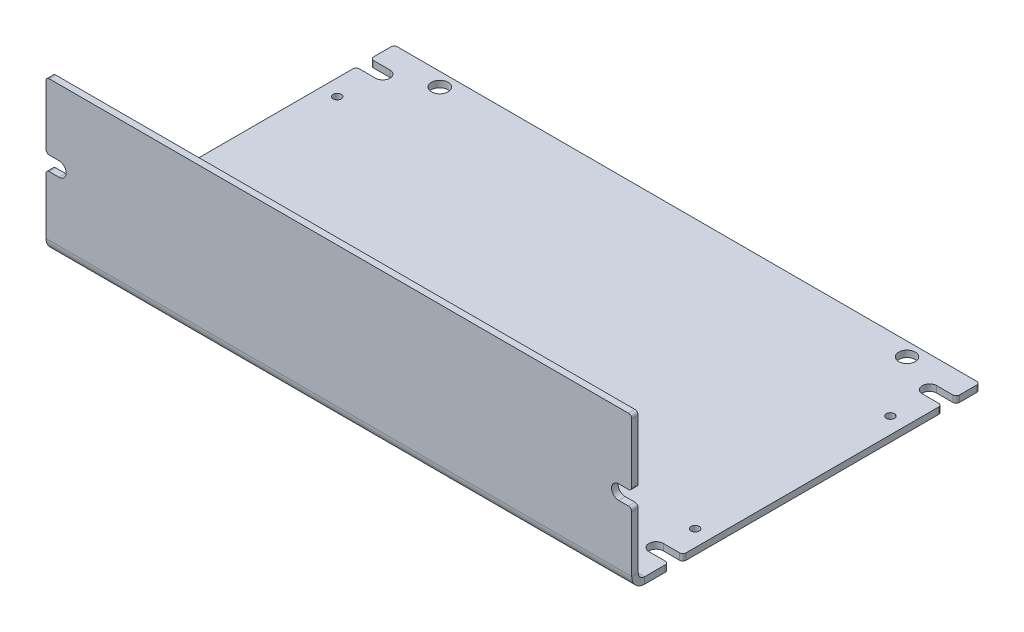
SolidWorks part; units mm, degrees
note: The reader was unsure of these and kept them because the rebuilt part matched: flange length of "Edge-Flange1".
material "AISI 304"
ref_plane "Front Plane" through (0, 0, 0) normal (0, 0, 1) x (1, 0, 0)
ref_plane "Top Plane" through (0, 0, 0) normal (0, 1, 0) x (1, 0, 0)
ref_plane "Right Plane" through (0, 0, 0) normal (1, 0, 0) x (0, 0, -1)
sketch "Sketch1" plane through (0, 0, 0) normal (0, 1, 0) x (1, 0, 0)
  line L1 (-90, 51.5) -> (90, 51.5)
  line L2 (-90, 51.5) -> (-90, -51.5)
  line L3 (-90, -51.5) -> (90, -51.5)
  line L4 (90, 51.5) -> (90, -51.5)
  line L5 (-90, 51.5) -> (90, -51.5) construction
  line L6 (-90, -51.5) -> (90, 51.5) construction
  point P0 (0, 0)
  dimension "D1" = 180
  dimension "D2" = 103
base flange "Base-Flange1" sketch "Sketch1" thickness 2 reverse thickness direction no parameters "D1"=2
edge flange "Edge-Flange1" sketch "Sketch8" flange angle 90 flange length 47 flange position bend outside bend radius 2 thickness 2 relief rectangular parameters "D6"=10
sketch "Sketch8" plane through (0, 0, -51.5) normal (0, 0, -1) x (-1, 0, 0)
  line L0 (-90, 24.7) -> (-86, 24.7)
  line L2 (-90, 0) -> (-90, 20.3)
  line L3 (-90, 45) -> (90, 45)
  line L4 (90, 45) -> (90, 24.7)
  line L5 (-86, 20.3) -> (-90, 20.3)
  line L7 (-90, 0) -> (90, 0) construction
  line L8 (-90, 0) -> (90, 0)
  line L9 (0, 0) -> (0, 45) construction
  line L10 (86, 20.3) -> (90, 20.3)
  line L11 (90, 24.7) -> (86, 24.7)
  line L12 (0, 22.5) -> (-86, 22.5) construction
  line L13 (-90, 24.7) -> (-90, 45)
  line L14 (90, 20.3) -> (90, 0)
  arc A0 (-86, 24.7) -> (-86, 20.3) centre (-86, 22.5) cw
  arc A1 (86, 24.7) -> (86, 20.3) centre (86, 22.5) ccw
  dimension "D2" = 2.2
  dimension "D1" = 45
  dimension "D3" = 4
bend "EdgeBend1" bend radius 2 bend angle 90 parameters "D5"=1
hole_wizard "Ø5.1 (5.1) Diameter Hole1" positions "Sketch9" profile "Sketch10" hole size "Ø5.1" standard "ISO" end condition through all
sketch "Sketch9" plane through (0, -2, 0) normal (0, -1, 0) x (-1, 0, 0)
  line L0 (90, -51.5) -> (-90, -51.5) construction
  point P0 (-71.8, -47.3)
  dimension "D1" = 4.2
  dimension "D2" = 71.8
sketch "Sketch10" plane through (71.8, -2, 47.3) normal (1, 0, 0) x (0, 0, -1)
  line L0 (0, 0) -> (0, 47)
  line L1 (0, 47) -> (2.55, 47)
  line L2 (2.55, 47) -> (2.55, 0)
  line L5 (2.55, 0) -> (0, 0)
  line L11 (0, -6.35) -> (0, 107.95) construction
  dimension "Thru Hole Dia." = 5.1
  dimension "Thru Hole Depth" = 47
pattern_linear "LPattern1" count 2 spacing 143.6 along (-1, 0, 0) count 2 spacing 93.6 along (0, 0, -1) of "Ø5.1 (5.1) Diameter Hole1"
hole_wizard "M3 Tapped Hole1" positions "Sketch11" profile "Sketch12" tap size "M3" standard "ISO" end condition through all
sketch "Sketch11" plane through (0, 0, 0) normal (0, 1, 0) x (1, 0, 0)
  line L0 (-90, 51.5) -> (-90, -51.5) construction
  line L1 (-90, -51.5) -> (90, -51.5) construction
  line L2 (0, 1) -> (0, -51.5) construction
  line L6 (0, 1) -> (90, 1) construction
  line L7 (90, -51.5) -> (90, 51.5) construction
  circle A0 centre (-71.8, -47.3) radius 2.55 construction
  point P0 (-85, -29)
  point P22 (85, -29)
  point P45 (-85, 31)
  point P46 (85, 31)
  dimension "D2" = 18.3
  dimension "D1" = 5
  dimension "D3" = 30
sketch "Sketch12" plane through (-85, 0, 29) normal (1, 0, 0) x (0, 0, 1)
  line L0 (0, 0) -> (0, 2)
  line L1 (0, 2) -> (1.25, 2)
  line L2 (1.25, 2) -> (1.25, 0)
  line L5 (1.25, 0) -> (0, 0)
  line L11 (0, -6.35) -> (0, 107.95) construction
  dimension "Thru Tap Drill Dia." = 2.5
  dimension "Thru Tap Drill Depth" = 2
cosmetic thread "Hole Thread1"
cosmetic thread "Hole Thread5"
cosmetic thread "Hole Thread6"
cosmetic thread "Hole Thread7"
sketch "Sketch13" plane through (0, 0, 0) normal (0, 1, 0) x (1, 0, 0)
  line L0 (-90, 44.2) -> (-84, 44.2)
  line L1 (-90, 51.5) -> (-90, -51.5) construction
  line L2 (-84, 39.8) -> (-90, 39.8)
  line L3 (-90, 39.8) -> (-90, 44.2)
  line L4 (0, 0) -> (-87.5, 0) construction
  line L5 (0, 0) -> (0, 55.5) construction
  line L6 (-90, 55.5) -> (90, 55.5) construction
  line L7 (-90, -39.8) -> (-90, -44.2)
  line L8 (-84, -39.8) -> (-90, -39.8)
  line L9 (-90, -44.2) -> (-84, -44.2)
  line L10 (90, -44.2) -> (84, -44.2)
  line L11 (84, -39.8) -> (90, -39.8)
  line L12 (90, -39.8) -> (90, -44.2)
  line L13 (90, 39.8) -> (90, 44.2)
  line L14 (84, 39.8) -> (90, 39.8)
  line L15 (90, 44.2) -> (84, 44.2)
  arc A0 (-84, 44.2) -> (-84, 39.8) centre (-84, 42) cw
  arc A1 (-84, -44.2) -> (-84, -39.8) centre (-84, -42) ccw
  arc A2 (84, -44.2) -> (84, -39.8) centre (84, -42) cw
  arc A3 (84, 44.2) -> (84, 39.8) centre (84, 42) ccw
  dimension "D1" = 2.2
  dimension "D2" = 6
  dimension "D3" = 42
extrude "Cut-Extrude1" cut sketch "Sketch13" against normal through all normal cut yes
fillet "Fillet1" radius 1 16 edges at (-90, 45, -54.5) (-90, -1, 51.5) (90, -1, 51.5) (90, -1, 44.2) (90, -1, 39.8) (90, -1, -39.8) (90, -1, -44.2) (-90, -1, -44.2) (-90, -1, -39.8) (-90, -1, 44.2) (-90, -1, 39.8) (90, 45, -54.5) (90, 24.7, -54.5) (90, 20.3, -54.5) (-90, 24.7, -54.5) (-90, 20.3, -54.5)
move or copy body "Body-Move/Copy1" bodies to move or copy 123 copy no rotation origin (0, 0, 0) rotation axis (0, 1, 0) rotation angle 180
sketch "Bend-Lines1" [suppressed] plane through (0, 0, 0) normal (0, 1, 0) x (1, 0, 0)
sketch "Bounding-Box1" [suppressed] plane through (0, 0, 0) normal (0, 1, 0) x (1, 0, 0)
sheet metal parameters "Sheet-Metal17" thickness 2 parameters "D1"=3
flat pattern "Flat-Pattern17" [suppressed]
sketch "Bend-Lines2" plane through (0, 0, 0) normal (0, 1, 0) x (1, 0, 0)
sketch "Bounding-Box2" [suppressed] plane through (0, 0, 0) normal (0, 1, 0) x (1, 0, 0)
sheet metal parameters "Sheet-Metal18" thickness 2 parameters "D1"=3
flat pattern "Flat-Pattern17" [suppressed]
sketch "Bend-Lines2" plane through (0, 0, 0) normal (0, 1, 0) x (1, 0, 0)
sketch "Bounding-Box2" [suppressed] plane through (0, 0, 0) normal (0, 1, 0) x (1, 0, 0)
bend of the flat pattern "Flatten-<EdgeBend1>1"
sheet metal parameters "Sheet-Metal19" thickness 2 parameters "D1"=3
flat pattern "Flat-Pattern17" [suppressed]
sketch "Bend-Lines2" plane through (0, 0, 0) normal (0, 1, 0) x (1, 0, 0)
sketch "Bounding-Box2" [suppressed] plane through (0, 0, 0) normal (0, 1, 0) x (1, 0, 0)
bend of the flat pattern "Flatten-<EdgeBend1>1"
sheet metal parameters "Sheet-Metal20" thickness 2 parameters "D1"=3
flat pattern "Flat-Pattern17" [suppressed]
sketch "Bend-Lines2" plane through (0, 0, 0) normal (0, 1, 0) x (1, 0, 0)
sketch "Bounding-Box2" [suppressed] plane through (0, 0, 0) normal (0, 1, 0) x (1, 0, 0)
bend of the flat pattern "Flatten-<EdgeBend1>1"
sheet metal parameters "Sheet-Metal21" thickness 2 parameters "D1"=3
flat pattern "Flat-Pattern17" [suppressed]
sketch "Bend-Lines2" plane through (0, 0, 0) normal (0, 1, 0) x (1, 0, 0)
sketch "Bounding-Box2" [suppressed] plane through (0, 0, 0) normal (0, 1, 0) x (1, 0, 0)
bend of the flat pattern "Flatten-<EdgeBend1>1"
sheet metal parameters "Sheet-Metal23" thickness 2 parameters "D1"=3
flat pattern "Flat-Pattern17" [suppressed]
sketch "Bend-Lines2" plane through (0, 0, 0) normal (0, 1, 0) x (1, 0, 0)
  line L0 (87.5, 50.8562) -> (-87.5, 50.8562) construction
  line L1 (87.5, 50.8562) -> (-87.5, 50.8562) construction
sketch3d "Bounding-Box2" [suppressed]
  line L0 (87.5, -52.5, 0) -> (-87.5, -52.5, 0) construction
  line L1 (87.5, 96.2124, 0) -> (-87.5, 96.2124, 0) construction
  line L2 (87.5, -52.5, 0) -> (87.5, 96.2124, 0) construction
  line L3 (-87.5, -52.5, 0) -> (-87.5, 96.2124, 0) construction
bend of the flat pattern "Flatten-<EdgeBend1>1"
sheet metal parameters "Sheet-Metal24" thickness 2 parameters "D1"=3
flat pattern "Flat-Pattern17"
sketch "Bend-Lines2" plane through (0, 0, 0) normal (0, 1, 0) x (1, 0, 0)
  line L0 (-90, -53.8562) -> (90, -53.8562) construction
  line L1 (-90, -53.8562) -> (90, -53.8562) construction
sketch3d "Bounding-Box2" [suppressed]
  line L0 (-90, 51.5, 0) -> (90, 51.5, 0) construction
  line L1 (-90, -99.2124, 0) -> (90, -99.2124, 0) construction
  line L2 (-90, 51.5, 0) -> (-90, -99.2124, 0) construction
  line L3 (90, 51.5, 0) -> (90, -99.2124, 0) construction
bend of the flat pattern "Flatten-<EdgeBend1>1"
